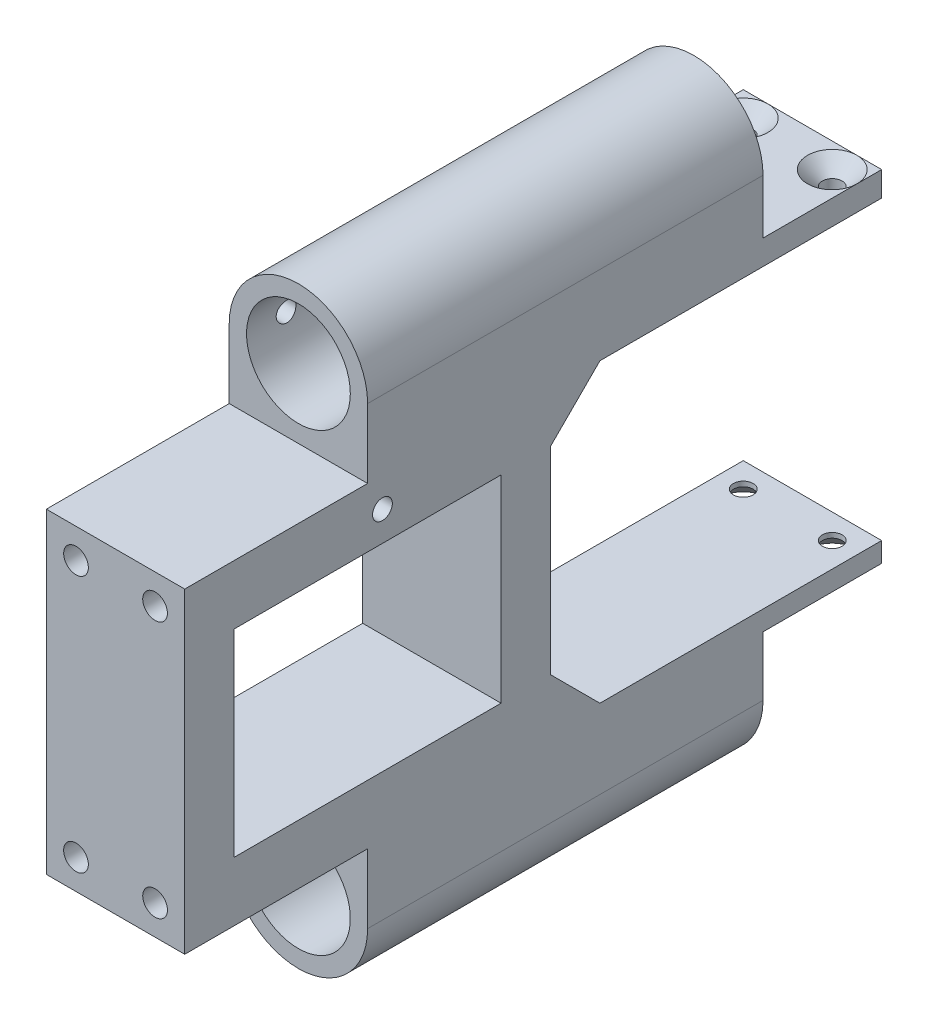
SolidWorks part; units mm, degrees
material "1060 合金"
ref_plane "前视基准面" through (0, 0, 0) normal (0, 0, 1) x (1, 0, 0)
ref_plane "上视基准面" through (0, 0, 0) normal (0, 1, 0) x (1, 0, 0)
ref_plane "右视基准面" through (0, 0, 0) normal (1, 0, 0) x (0, 0, -1)
sketch "草图1" plane through (0, 0, 0) normal (0, 0, 1) x (1, 0, 0)
  line L1 (-14, 64) -> (14, 64)
  line L2 (-14, 64) -> (-14, 0)
  line L3 (-14, 0) -> (14, 0)
  line L4 (14, 64) -> (14, 0)
  point P4 (0, 0)
  dimension "D1" = 28
  dimension "D2" = 64
extrude "凸台-拉伸1" add sketch "草图1" along normal blind 74
sketch "草图2" plane through (0, 0, 74) normal (0, 0, 1) x (1, 0, 0)
  line L0 (14, 64) -> (-14, 64) construction
  line L1 (-8, 58) -> (8, 6) construction
  line L4 (0, 0) -> (0, 64) construction
  circle A0 centre (-8, 58) radius 2.5
  circle A1 centre (8, 58) radius 2.5
  circle A2 centre (-8, 6) radius 2.5
  circle A3 centre (8, 6) radius 2.5
  circle A4 centre (0, -7.5) radius 7.5 construction
  point P10 (0, 32)
  dimension "D1" = 5
  dimension "D6" = 15
  dimension "D2" = 52
  dimension "D3" = 16
  dimension "D7" = 7.5
extrude "切除-拉伸1" cut sketch "草图2" against normal blind 10
sketch "草图3" plane through (0, 0, 0) normal (1, 0, 0) x (0, 0, -1)
  line L0 (-74, 0) -> (-74, 64) construction
  line L1 (-64, 52) -> (-10, 52)
  line L2 (-64, 52) -> (-64, 12)
  line L3 (-64, 12) -> (-10, 12)
  line L4 (-10, 52) -> (-10, 12)
  line L5 (-74, 64) -> (0, 64) construction
  line L6 (0, 0) -> (0, 64) construction
  line L7 (-74, 0) -> (0, 0) construction
  dimension "D1" = 10
  dimension "D2" = 12
  dimension "D3" = 10
  dimension "D4" = 12
extrude "切除-拉伸2" cut sketch "草图3" against normal through all both and the other way through all
ref_plane "基准面1" through (0, 0, -16) normal (0, 0, 1) x (1, 0, 0)
ref_plane "基准面2" through (0, 0, 37) normal (0, 0, 1) x (1, 0, 0)
sketch "草图4" plane through (0, 0, 37) normal (0, 0, -1) x (-1, 0, 0)
  line L0 (-14, 0) -> (-14, 64) construction
  line L5 (14, 32) -> (-14, 32) construction
  line L10 (14, 64) -> (14, 0) construction
  line L12 (-14, 2) -> (14, 2)
  line L13 (-14, 2) -> (-14, -14)
  line L14 (14, 2) -> (14, -14)
  line L15 (14, 0) -> (-14, 0) construction
  line L16 (14, 62) -> (14, 78)
  line L17 (-14, 62) -> (-14, 78)
  line L18 (-14, 62) -> (14, 62)
  circle A1 centre (0, -14) radius 10.5 construction
  circle A2 centre (0, -14) radius 7.5 construction
  arc A3 (-14, -14) -> (14, -14) centre (0, -14) ccw
  circle A4 centre (0, 78) radius 7.5 construction
  circle A5 centre (0, 78) radius 10.5 construction
  arc A6 (-14, 78) -> (14, 78) centre (0, 78) cw
  point P23 (0, 2)
  dimension "D4" = 21
  dimension "D5" = 14
  dimension "D6" = 15
  dimension "D7" = 16
  dimension "D8" = 2
extrude "凸台-拉伸2" add sketch "草图4" along normal blind 80
sketch "草图6" plane through (0, 0, 37) normal (0, 0, -1) x (-1, 0, 0)
  line L0 (14, 32) -> (-14, 32) construction
  line L1 (14, 62) -> (14, 2) construction
  line L2 (-14, 2) -> (-14, 62) construction
  circle A2 centre (0, -14) radius 10.5
  circle A3 centre (0, 78) radius 10.5
  dimension "D1" = 21
extrude "切除-拉伸3" cut sketch "草图6" along normal through all
sketch "草图11" plane through (0, 0, 0) normal (0, 0, -1) x (-1, 0, 0)
  line L0 (14, -14) -> (14, 2) construction
  line L1 (-14, 64) -> (14, 64) construction
  line L3 (-14, 64) -> (14, 64) construction
  line L4 (14, 62) -> (-14, 62)
  line L5 (14, 62) -> (14, 2) construction
  line L6 (-14, 2) -> (-14, 62) construction
  line L7 (-14, 62) -> (-14, 67)
  line L8 (-14, 67) -> (14, 67)
  line L9 (14, 67) -> (14, 62)
  line L14 (-14, 2) -> (14, 2)
  line L15 (-14, 2) -> (-14, -2)
  line L16 (-14, -2) -> (14, -2)
  line L17 (14, 2) -> (14, -2)
  dimension "D1" = 2
  dimension "D2" = 5
  dimension "D3" = 4
extrude "凸台-拉伸5" add sketch "草图11" along normal blind 67
sketch "草图12" plane through (0, 67, 0) normal (0, 1, 0) x (1, 0, 0)
  line L0 (-14, 67) -> (-14, 43) construction
  line L1 (-14, 67) -> (14, 67) construction
  line L2 (14, 67) -> (14, 43) construction
  circle A0 centre (-9, 62) radius 2
  circle A1 centre (9, 62) radius 2
  dimension "D1" = 4
  dimension "D2" = 5
  dimension "D3" = 5
  dimension "D4" = 5
extrude "切除-拉伸8" cut sketch "草图12" against normal through all
chamfer "倒角1" distance 10 angle 45 2 edges at (0, 62, 0) (0, 2, 0)
ref_plane "基准面3" through (0, 0, -3) normal (0, 0, 1) x (1, 0, 0)
sketch "草图13" plane through (0, 0, -3) normal (0, 0, 1) x (1, 0, 0)
  line L0 (-14, 32) -> (14, 32) construction
  line L1 (-14, 64) -> (-14, 0) construction
  line L2 (14, 0) -> (14, 64) construction
  circle A0 centre (0, 78) radius 9.5
  circle A2 centre (0, 78) radius 10.5 construction
  circle A3 centre (0, 78) radius 10.5
  circle A4 centre (0, -14) radius 10.5
  circle A5 centre (0, -14) radius 9.5
  dimension "D1" = 19
extrude "凸台-拉伸6" add sketch "草图13" along normal mid plane 50
sketch "草图14" plane through (0, 0, 0) normal (1, 0, 0) x (0, 0, -1)
  line L0 (-74, 32) -> (44.1527, 32) construction
  line L1 (-74, 0) -> (-74, 64) construction
  line L2 (-37, 92) -> (-37, 78) construction
  line L3 (43, 78) -> (43, 92) construction
  line L4 (-37, 88.5) -> (-37, 67.5) construction
  line L5 (-37, 88.5) -> (-37, 67.5) construction
  circle A0 centre (-29, 78) radius 2
  circle A1 centre (35, 78) radius 2
  circle A2 centre (35, -14) radius 2
  circle A3 centre (-29, -14) radius 2
  point P22 (-37, 78)
  dimension "D1" = 4
  dimension "D2" = 8
  dimension "D3" = 8
extrude "切除-拉伸9" cut sketch "草图14" against normal through all
sketch "草图15" plane through (-14, 0, 0) normal (-1, 0, 0) x (0, 0, 1)
  line L0 (74, 64) -> (37, 64) construction
  line L1 (74, 64) -> (74, 0) construction
  circle A0 centre (34, 58) radius 2
  dimension "D1" = 4
  dimension "D2" = 6
  dimension "D3" = 40
extrude "切除-拉伸10" cut sketch "草图15" against normal through all
chamfer "倒角2" distance 3 angle 45 4 edges at (-9, -2, -60) (9, -2, -60) (-9, 67, -60) (9, 67, -60)
